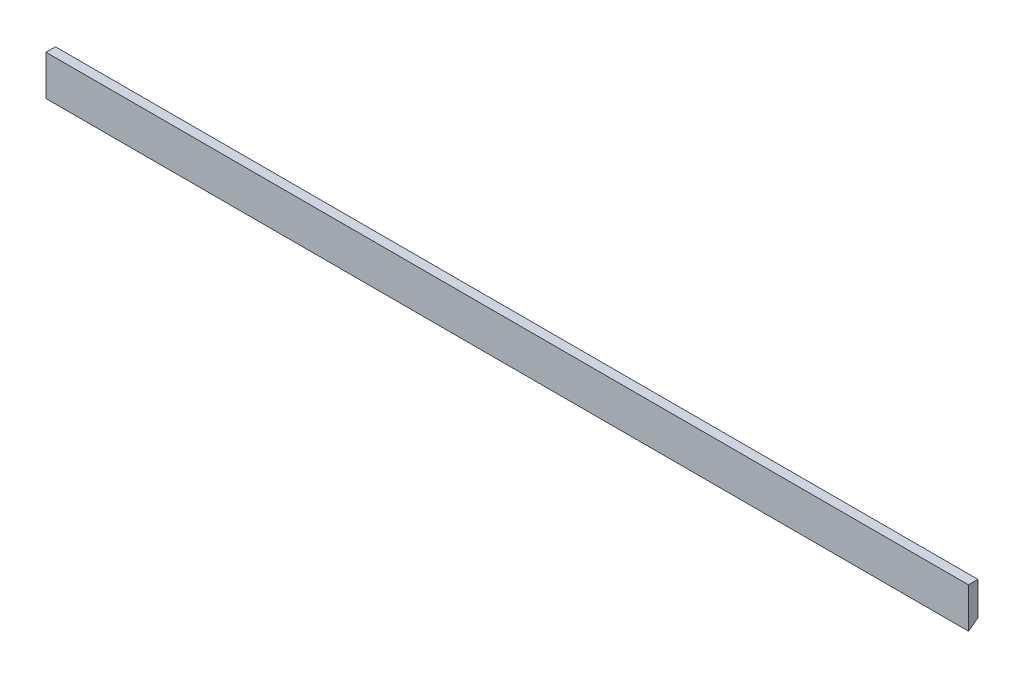
SolidWorks part; units mm, degrees
material "Balsa"
ref_plane "Front Plane" through (0, 0, 0) normal (0, 0, 1) x (1, 0, 0)
ref_plane "Top Plane" through (0, 0, 0) normal (0, 1, 0) x (1, 0, 0)
ref_plane "Right Plane" through (0, 0, 0) normal (1, 0, 0) x (0, 0, -1)
sketch "Sketch2" plane through (0, 0, 0) normal (1, 0, 0) x (0, 0, -1)
  line L1 (-1.5875, 6.745) -> (1.5875, 6.745)
  line L2 (-1.5875, 6.745) -> (-1.5875, -6.745)
  line L3 (-1.5875, -6.745) -> (1.5875, -6.745)
  line L4 (1.5875, 6.745) -> (1.5875, -6.745)
  line L5 (-1.5875, 6.745) -> (1.5875, -6.745) construction
  line L6 (-1.5875, -6.745) -> (1.5875, 6.745) construction
  point P0 (0, 0)
  dimension "D1" = 3.175
  dimension "D2" = 13.49
extrude "Boss-Extrude1" add sketch "Sketch2" along normal blind 310
chamfer "Chamfer1" distance 3.175 angle 36.5 1 edges at (155, -6.745, -1.5875) first distance on face at (155, -6.745, 0)
